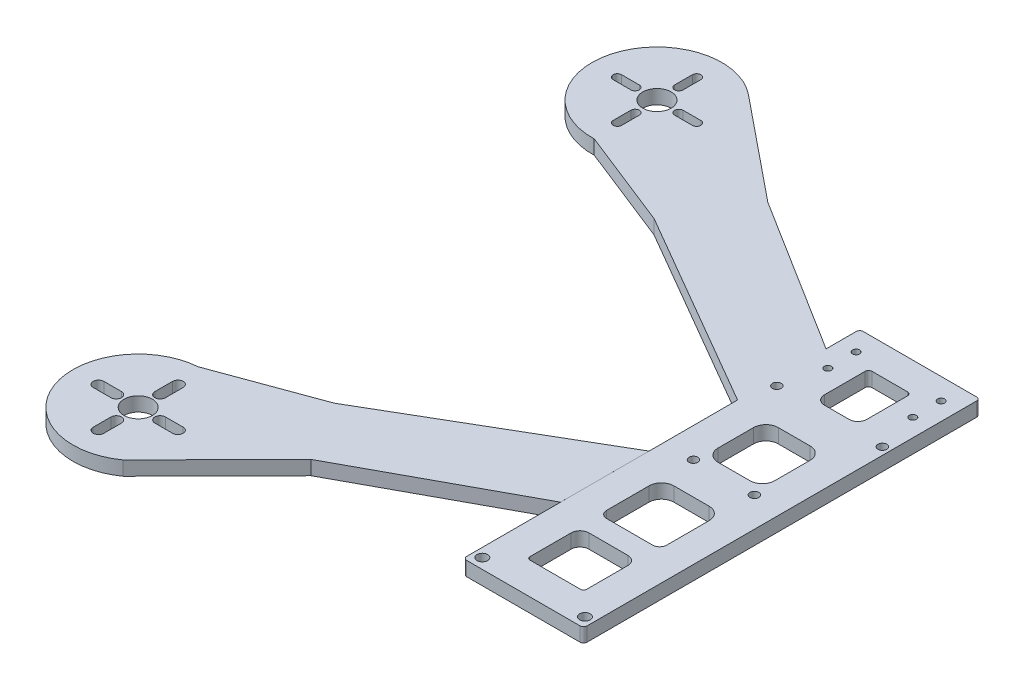
SolidWorks part; units mm, degrees
ref_plane "Front Plane" through (0, 0, 0) normal (0, 0, 1) x (1, 0, 0)
ref_plane "Top Plane" through (0, 0, 0) normal (0, 1, 0) x (1, 0, 0)
ref_plane "Right Plane" through (0, 0, 0) normal (1, 0, 0) x (0, 0, -1)
sketch "Frame Sketch" plane through (0, 0, 0) normal (0, 1, 0) x (1, 0, 0)
  line L0 (0, 0) -> (0, 126.6085) construction
  line L6 (-17, 46.5) -> (-61.0621, 74.114)
  line L11 (0, 0) -> (0, -105.8001) construction
  line L23 (-16, 56) -> (16, 56)
  line L24 (-17, 55) -> (-17, -55)
  line L25 (-16, -56) -> (16, -56)
  line L26 (17, 55) -> (17, -55)
  line L27 (-17, 56) -> (17, -56) construction
  line L28 (-17, -56) -> (17, 56) construction
  line L44 (-7.1404, -47) -> (7.1404, -47)
  line L45 (-8, -46.1404) -> (-8, -34.5)
  line L46 (-5.5, -32) -> (5.5, -32)
  line L47 (8, -46.1404) -> (8, -34.5)
  line L48 (-8, -47) -> (8, -32) construction
  line L49 (-8, -32) -> (8, -47) construction
  line L50 (6.5, -26) -> (-6.5, -26)
  line L51 (8.5, -24) -> (8.5, -12)
  line L52 (5, -8.5) -> (-5, -8.5)
  line L53 (-8.5, -24) -> (-8.5, -12)
  line L54 (8.5, -26) -> (-8.5, -8.5) construction
  line L55 (8.5, -8.5) -> (-8.5, -26) construction
  line L56 (-4.5, 3.5) -> (4.5, 3.5)
  line L57 (-8, 7) -> (-8, 17)
  line L58 (-4.5, 20.5) -> (4.5, 20.5)
  line L59 (8, 7) -> (8, 17)
  line L60 (-8, 3.5) -> (8, 20.5) construction
  line L61 (-8, 20.5) -> (8, 3.5) construction
  line L62 (-3.5, 32.5) -> (3.5, 32.5)
  line L63 (-6, 35) -> (-6, 46.5)
  line L64 (-5, 47.5) -> (5, 47.5)
  line L65 (6, 35) -> (6, 46.5)
  line L66 (-6, 32.5) -> (6, 47.5) construction
  line L67 (-6, 47.5) -> (6, 32.5) construction
  line L88 (-17, 21.5) -> (-73.2257, 54.114)
  line L89 (-17, 40.3719) -> (-17, -14.3719)
  line L91 (-17, 46.5) -> (-17, 21.5)
  line L92 (-61.0621, 74.114) -> (-90.179, 97.7457)
  line L94 (-73.2257, 54.114) -> (-101.13, 65.1299)
  line L95 (-101.7528, 94.6653) -> (-101.7528, 89.6653) construction
  line L96 (-100.5494, 94.6653) -> (-100.5494, 89.6653)
  line L97 (-102.9563, 94.6653) -> (-102.9563, 89.6653)
  line L101 (-101.7528, 98.1406) -> (-101.7528, 70.7941) construction
  line L103 (-116.122, 83.4854) -> (-86.6644, 83.4854) construction
  line L105 (-101.7528, 72.3054) -> (-101.7528, 77.3054) construction
  line L106 (-100.5494, 72.3054) -> (-100.5494, 77.3054)
  line L107 (-102.9563, 72.3054) -> (-102.9563, 77.3054)
  line L108 (-112.9528, 83.4854) -> (-107.9528, 83.4854) construction
  line L109 (-112.9528, 84.6854) -> (-107.9528, 84.6854)
  line L110 (-112.9528, 82.2854) -> (-107.9528, 82.2854)
  line L111 (-90.5528, 83.4854) -> (-95.5528, 83.4854) construction
  line L112 (-90.5528, 84.6854) -> (-95.5528, 84.6854)
  line L113 (-90.5528, 82.2854) -> (-95.5528, 82.2854)
  line L114 (0, 0) -> (48.4742, 0) construction
  line L115 (48.4742, 0) -> (-39.8302, 0) construction
  line L116 (-62.7163, -53.2815) -> (-89.0979, -79.9323)
  line L117 (-17.0012, -28.5) -> (-62.7163, -53.2815)
  line L118 (-17.0012, -28.5) -> (-17.0012, -3.5)
  line L119 (-17.0012, -3.5) -> (-73.1618, -36.226)
  line L120 (-73.1618, -36.226) -> (-101.3254, -46.5609)
  line L121 (-99.8523, -53.747) -> (-99.8523, -58.747) construction
  line L122 (-98.3523, -53.747) -> (-98.3523, -58.747)
  line L123 (-101.3523, -53.747) -> (-101.3523, -58.747)
  line L124 (-99.8523, -49.0383) -> (-99.8523, -77.2243) construction
  line L126 (-111.0523, -64.947) -> (-106.0523, -64.947) construction
  line L127 (-99.8523, -76.147) -> (-99.8523, -71.147) construction
  line L128 (-98.3523, -76.147) -> (-98.3523, -71.147)
  line L129 (-101.3523, -76.147) -> (-101.3523, -71.147)
  line L134 (-111.0523, -63.447) -> (-106.0523, -63.447)
  line L135 (-111.0523, -66.447) -> (-106.0523, -66.447)
  line L136 (-88.6523, -64.947) -> (-93.6523, -64.947) construction
  line L137 (-88.6523, -63.447) -> (-93.6523, -63.447)
  line L138 (-88.6523, -66.447) -> (-93.6523, -66.447)
  arc A8 (17, 55) -> (16, 56) centre (16, 55) ccw
  arc A9 (17, -55) -> (16, -56) centre (16, -55) cw
  arc A10 (-16, 56) -> (-17, 55) centre (-16, 55) ccw
  arc A11 (-16, -56) -> (-17, -55) centre (-16, -55) cw
  circle A12 centre (-14.5, -53.1) radius 1.5
  circle A13 centre (14.5, -53.1) radius 1.5
  arc A14 (8, -46.1404) -> (7.1404, -47) centre (7.1404, -46.1404) cw
  arc A15 (-7.1404, -47) -> (-8, -46.1404) centre (-7.1404, -46.1404) cw
  arc A16 (-8, -34.5) -> (-5.5, -32) centre (-5.5, -34.5) cw
  arc A17 (5.5, -32) -> (8, -34.5) centre (5.5, -34.5) cw
  arc A18 (8.5, -24) -> (6.5, -26) centre (6.5, -24) cw
  arc A19 (-8.5, -24) -> (-6.5, -26) centre (-6.5, -24) ccw
  arc A20 (8.5, -12) -> (5, -8.5) centre (5, -12) ccw
  arc A21 (-5, -8.5) -> (-8.5, -12) centre (-5, -12) ccw
  arc A22 (-4.5, 3.5) -> (-8, 7) centre (-4.5, 7) cw
  arc A23 (8, 7) -> (4.5, 3.5) centre (4.5, 7) cw
  arc A24 (-4.5, 20.5) -> (-8, 17) centre (-4.5, 17) ccw
  arc A25 (8, 17) -> (4.5, 20.5) centre (4.5, 17) ccw
  arc A26 (-3.5, 32.5) -> (-6, 35) centre (-3.5, 35) cw
  arc A27 (6, 35) -> (3.5, 32.5) centre (3.5, 35) cw
  arc A28 (-5, 47.5) -> (-6, 46.5) centre (-5, 46.5) ccw
  arc A29 (6, 46.5) -> (5, 47.5) centre (5, 46.5) ccw
  circle A30 centre (12, 50) radius 1
  circle A31 centre (12, 42) radius 1
  circle A32 centre (-12, 50) radius 1
  circle A33 centre (-12, 42) radius 1
  circle A34 centre (-14.9, 30.5) radius 1.25
  circle A35 centre (-8.6019, 0.6404) radius 1.25
  circle A36 centre (8.6019, 0.6404) radius 1.25
  circle A37 centre (14.9, 30.5) radius 1.25
  arc A39 (-90.179, 97.7457) -> (-101.13, 65.1299) centre (-101.7528, 83.4854) ccw
  circle A41 centre (-101.7528, 83.4854) radius 4
  arc A42 (-100.5494, 94.6653) -> (-102.9563, 94.6653) centre (-101.7528, 94.6653) ccw
  arc A43 (-102.9563, 89.6653) -> (-100.5494, 89.6653) centre (-101.7528, 89.6653) ccw
  arc A44 (-100.5494, 72.3054) -> (-102.9563, 72.3054) centre (-101.7528, 72.3054) cw
  arc A45 (-102.9563, 77.3054) -> (-100.5494, 77.3054) centre (-101.7528, 77.3054) cw
  arc A46 (-112.9528, 84.6854) -> (-112.9528, 82.2854) centre (-112.9528, 83.4854) ccw
  arc A47 (-107.9528, 82.2854) -> (-107.9528, 84.6854) centre (-107.9528, 83.4854) ccw
  arc A48 (-90.5528, 84.6854) -> (-90.5528, 82.2854) centre (-90.5528, 83.4854) cw
  arc A49 (-95.5528, 82.2854) -> (-95.5528, 84.6854) centre (-95.5528, 83.4854) cw
  arc A50 (-89.0979, -79.9323) -> (-101.3254, -46.5609) centre (-99.8523, -64.947) cw
  circle A51 centre (-99.8523, -64.947) radius 4
  arc A54 (-98.3523, -53.747) -> (-101.3523, -53.747) centre (-99.8523, -53.747) ccw
  arc A55 (-101.3523, -58.747) -> (-98.3523, -58.747) centre (-99.8523, -58.747) ccw
  arc A56 (-98.3523, -76.147) -> (-101.3523, -76.147) centre (-99.8523, -76.147) cw
  arc A57 (-101.3523, -71.147) -> (-98.3523, -71.147) centre (-99.8523, -71.147) cw
  arc A62 (-111.0523, -63.447) -> (-111.0523, -66.447) centre (-111.0523, -64.947) ccw
  arc A63 (-106.0523, -66.447) -> (-106.0523, -63.447) centre (-106.0523, -64.947) ccw
  arc A64 (-88.6523, -63.447) -> (-88.6523, -66.447) centre (-88.6523, -64.947) cw
  arc A65 (-93.6523, -66.447) -> (-93.6523, -63.447) centre (-93.6523, -64.947) cw
  point P23 (-101.7528, 92.1653)
  point P42 (-101.7528, 74.8054)
  point P52 (0, -39.5)
  point P69 (0, -17.25)
  point P86 (0, 12)
  point P103 (0, 40)
  point P141 (-110.4528, 83.4854)
  point P148 (-93.0528, 83.4854)
  point P162 (-99.8523, -56.247)
  point P173 (-99.8523, -73.647)
  point P178 (-108.5523, -64.947)
  point P185 (-91.1523, -64.947)
  point P190 (0, 0)
  dimension "D6" = 9.5
  dimension "D7" = 2.9
  dimension "D8" = 2.5
  dimension "D5" = 17.5
  dimension "D11" = 9
  dimension "D12" = 9
  dimension "D13" = 12
  dimension "D14" = 52
  dimension "D17" = 25
  dimension "D18" = 20
  dimension "D19" = 65
  dimension "D20" = 37.5
  dimension "D23" = 30
  dimension "D24" = 8
  dimension "D25" = 1
  dimension "D26" = 5
  dimension "D30" = 6
  dimension "D31" = 6
  dimension "D32" = 8
  dimension "D33" = 2.4069
  dimension "D34" = 5
  dimension "D36" = 2.5
  dimension "D37" = 6.18
  dimension "D38" = 2.1
  dimension "D39" = 6.2
  dimension "D47" = 8
  dimension "D49" = 5
  dimension "D50" = 6.2
  dimension "D52" = 5
  dimension "D53" = 3
  dimension "D51" = 6.2
  dimension "D3" = 112
  dimension "D4" = 34
  dimension "D9" = 15
  dimension "D10" = 16
  dimension "D15" = 17
  dimension "D16" = 6
  dimension "D21" = 17
  dimension "D22" = 16
  dimension "D27" = 12
  dimension "D28" = 15
  dimension "D29" = 12
  dimension "D35" = 2.4
  dimension "D40" = 25
  dimension "D41" = 20
  dimension "D42" = 30
  dimension "D43" = 37.5
  dimension "D44" = 65
  dimension "D45" = 52
  dimension "D46" = 25
  dimension "D48" = 3
extrude "Frame Bottom Plate" add sketch "Frame Sketch" along normal blind 4
